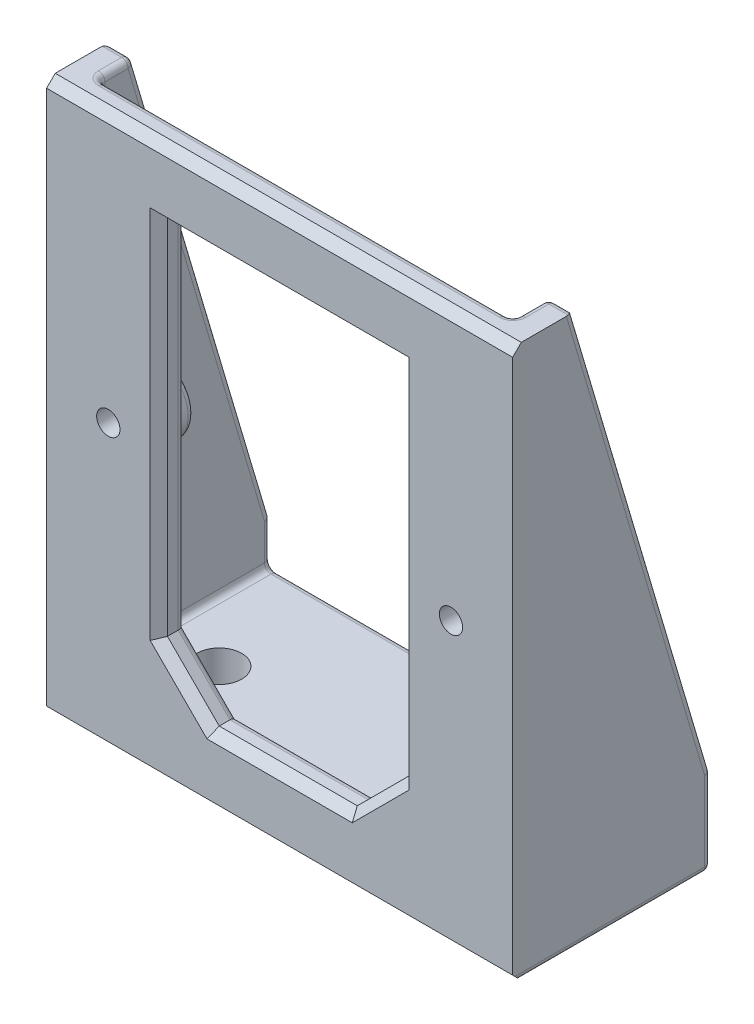
SolidWorks part; units mm, degrees
material "ABS"
ref_plane "Front Plane" through (0, 0, 0) normal (0, 0, 1) x (1, 0, 0)
ref_plane "Top Plane" through (0, 0, 0) normal (0, 1, 0) x (1, 0, 0)
ref_plane "Right Plane" through (0, 0, 0) normal (1, 0, 0) x (0, 0, -1)
sketch "Sketch1" plane through (0, 0, 0) normal (0, 0, 1) x (1, 0, 0)
  line L0 (-27, 0) -> (27, 0)
  line L1 (27, 0) -> (27, 64)
  line L2 (27, 64) -> (-27, 64)
  line L3 (-27, 64) -> (-27, 0)
  line L4 (0, 64) -> (0, 0) construction
  line L5 (-8, 8) -> (8, 8)
  line L6 (8, 8) -> (14, 14)
  line L7 (14, 14) -> (14, 56)
  line L8 (14, 56) -> (-14, 56)
  line L9 (-14, 56) -> (-14, 14)
  line L10 (-14, 14) -> (-8, 8)
  line L11 (-26, 33) -> (26, 33) construction
  line L12 (0, 56) -> (0, 8) construction
  circle A0 centre (-19.85, 33) radius 1.35
  circle A1 centre (19.85, 33) radius 1.35
  point P2 (0, 0)
  point P10 (0, 8)
  point P11 (0, 56)
  dimension "D7" = 2.7
  dimension "D8" = 39.7
  dimension "D9" = 33
  dimension "D1" = 54
  dimension "D2" = 64
  dimension "D3" = 48
  dimension "D4" = 16
  dimension "D5" = 28
  dimension "D6" = 6
  dimension "D10" = 23
extrude "Boss-Extrude1" add sketch "Sketch1" along normal blind 3
sketch "Sketch2" plane through (27, 0, 0) normal (1, 0, 0) x (0, 0, -1)
  line L0 (0, 64) -> (0, 0)
  line L1 (0, 0) -> (20, 0)
  line L2 (-3, 0) -> (-3, 64) construction
  line L4 (20, 0) -> (20, 10)
  line L5 (4, 64) -> (20, 10)
  line L7 (4, 64) -> (0, 64)
  dimension "D1" = 23
  dimension "D3" = 10
  dimension "D4" = 4
extrude "Boss-Extrude2" add sketch "Sketch2" against normal blind 3
mirror "Mirror1" about plane through (0, 0, 0) normal (1, 0, 0) of "Boss-Extrude2"
sketch "Sketch3" plane through (0, 0, 0) normal (0, 0, -1) x (-1, 0, 0)
  line L0 (-19.85, 37) -> (-24, 37)
  line L1 (-24, 64) -> (-24, 0) construction
  line L2 (-19.85, 29) -> (-24, 29)
  line L3 (-24, 29) -> (-24, 37)
  line L4 (0, 64) -> (0, 0) construction
  line L5 (-24, 64) -> (24, 64) construction
  line L6 (24, 29) -> (24, 37)
  line L7 (19.85, 29) -> (24, 29)
  line L8 (19.85, 37) -> (24, 37)
  arc A0 (-19.85, 29) -> (-19.85, 37) centre (-19.85, 33) ccw
  arc A1 (19.85, 29) -> (19.85, 37) centre (19.85, 33) cw
  dimension "D1" = 8
extrude "Boss-Extrude3" add sketch "Sketch3" along normal blind 3
sketch "Sketch4" plane through (0, 0, 0) normal (0, 0, 1) x (1, 0, 0)
  circle A0 centre (-19.85, 33) radius 1.35 construction
  circle A1 centre (19.85, 33) radius 1.35 construction
  circle A2 centre (-19.85, 33) radius 1.35
  circle A3 centre (19.85, 33) radius 1.35
extrude "Cut-Extrude2" cut sketch "Sketch4" against normal up to surface (3 mm away) up to face at (20.925, 33, -3)
sketch "Sketch5" plane through (0, 0, 0) normal (0, -1, 0) x (1, 0, 0)
  line L0 (-24, 0) -> (-24, -20)
  line L1 (-24, 0) -> (24, 0)
  line L2 (24, 0) -> (24, -20)
  line L3 (24, 0) -> (24, -20) construction
  line L4 (-24, -20) -> (24, -20)
  line L5 (24, -7) -> (-24, -7) construction
  line L6 (-27, 3) -> (27, 3) construction
  circle A0 centre (-17, -7) radius 2.6
  circle A1 centre (17, -7) radius 2.6
  dimension "D2" = 5.2
  dimension "D3" = 7
  dimension "D4" = 7
  dimension "D1" = 10
extrude "Boss-Extrude4" add sketch "Sketch5" against normal blind 5
fillet "Fillet3" radius 0.75 49 edges at (-24, 7.5, -20) (24, 7.5, -20) (24, 5, -10) (0, 5, -20) (-24, 5, -10) (-11, 11, 0) (0, 8, 0) (11, 11, 0) (14, 35, 0) (0, 56, 0) (-14, 35, 0) (24, 37, -12) (25.5, 64, -4) (25.5, 10, -20) (0, 0, -20) (27, 5, -20) (27, 37, -12) (-25.5, 64, -4) (-27, 5, -20) (-27, 37, -12) (-25.5, 10, -20) (-24, 64, -2) (-24, 50.5, 0) (-24, 37, -12) (27, 0, -8.5) (-27, 0, -8.5) (15.85, 33, 0) (21.925, 37, 0) (24, 37, -1.5) (21.925, 29, 0) (24, 29, -1.5) (15.85, 33, -3) (21.925, 37, -3) (24, 33, -3) (21.925, 29, -3) (-24, 17, 0) (-15.85, 33, 0) (-21.925, 29, 0) (-24, 29, -1.5) (-21.925, 37, 0) (-24, 37, -1.5) (-15.85, 33, -3) (-21.925, 29, -3) (-24, 33, -3) (-21.925, 37, -3)
chamfer "Chamfer1" distance 1 angle 45 12 edges at (0, 56, 3) (14, 35, 3) (11, 11, 3) (0, 8, 3) (-11, 11, 3) (-14, 35, 3) (0, 64, 3) (-27, 32.375, 3) (27, 32.375, 3) (-26.7803, 0.2197, 3) (26.7803, 0.2197, 3) (0, 0, 3)
